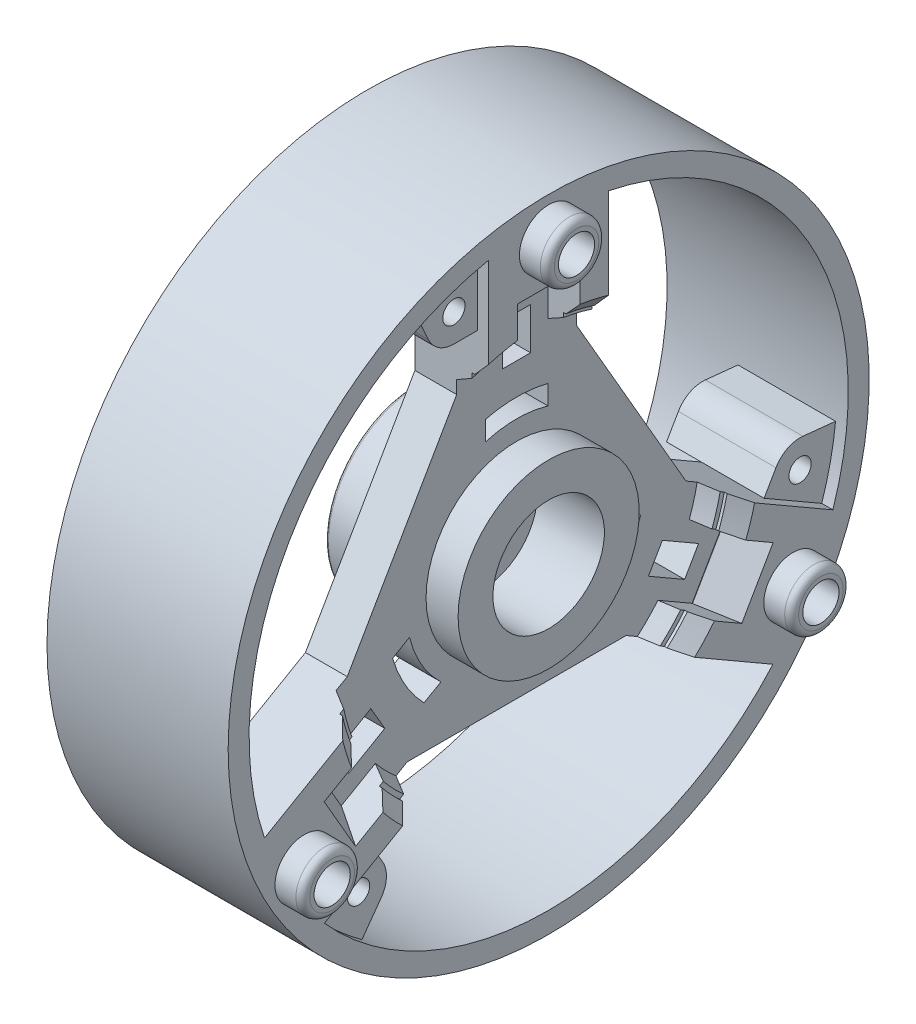
SolidWorks part; units mm, degrees
ref_plane "Front" through (0, 0, 0) normal (0, 0, 1) x (1, 0, 0)
ref_plane "Top" through (0, 0, 0) normal (0, 1, 0) x (1, 0, 0)
ref_plane "Right" through (0, 0, 0) normal (1, 0, 0) x (0, 0, -1)
sketch "草图1" plane through (0, 0, 0) normal (0, 0, 1) x (1, 0, 0)
  line L0 (-28.9493, 0) -> (20.3261, 0) construction
  line L1 (0, 28.587) -> (0, -29.6739) construction
  line L2 (-13, 23) -> (0, 23)
  line L3 (0, 23) -> (0, 21.5)
  line L4 (0, 21.5) -> (-2.3, 21.5)
  line L5 (-2.3, 21.5) -> (-2.3, 6.5)
  line L6 (-2.3, 6.5) -> (0, 6.5)
  line L7 (0, 6.5) -> (0, 4)
  line L8 (0, 4) -> (-4.8, 4)
  line L9 (-4.8, 4) -> (-4.8, 2.5)
  line L10 (-4.8, 2.5) -> (-9.5, 2.5)
  line L11 (-9.5, 2.5) -> (-9.5, 6.5)
  line L12 (-9.5, 6.5) -> (-5.3, 6.5)
  line L13 (-5.3, 6.5) -> (-5.3, 21.5)
  line L14 (-5.3, 21.5) -> (-13, 21.5)
  line L15 (-13, 21.5) -> (-13, 23)
  point P7 (0, 22.25)
  dimension "D1" = 46
  dimension "D2" = 5
  dimension "D3" = 8
  dimension "D4" = 4.8
  dimension "D5" = 9.5
  dimension "D6" = 2.3
  dimension "D7" = 3
  dimension "D8" = 13
  dimension "D9" = 43
  dimension "D10" = 1.5
  dimension "D11" = 13
revolve "旋转1" add sketch "草图1" angle 360 about L0
sketch "草图2" plane through (-2.3, 0, 0) normal (1, 0, 0) x (0, 0, -1)
  line L0 (-28.8225, 0) -> (32.6158, 0) construction
  line L1 (0, 27.0503) -> (0, -29.2143) construction
  line L2 (0, 0) -> (-26.977, 15.5752) construction
  line L3 (0, 0) -> (25.1673, 14.5303) construction
  line L4 (-4.3, 21.0656) -> (-4.3, 11.5522)
  line L5 (4.3, 21.0656) -> (4.3, 11.5522) construction
  line L6 (0, 0) -> (-25.6049, -14.783) construction
  line L7 (-20.3934, -6.8089) -> (-12.1545, -2.0522)
  line L8 (-4.3, 11.5522) -> (-12.1545, -2.0522)
  circle A0 centre (0, 0) radius 21.5 construction
  arc A1 (-4.3, 21.0656) -> (-20.3934, -6.8089) centre (0, 0) ccw
  dimension "D1" = 60
  dimension "D2" = 60
  dimension "D3" = 8.6
  dimension "D4" = 60
  dimension "D5" = 4.3
  dimension "D6" = 4.3
  dimension "D7" = 9.5
extrude "切除-拉伸1" cut sketch "草图2" against normal blind 10
pattern_circular "阵列(圆周)1" count 3 over 360 about axis through (-28.9493, 0, 0) along (-1, 0, 0) of "切除-拉伸1"
sketch "草图3" plane through (-2.3, 0, 0) normal (1, 0, 0) x (0, 0, -1)
  line L0 (0, 25.0293) -> (0, -25.5268) construction
  line L1 (-29.32, 0) -> (32.0561, 0) construction
  line L2 (-2.25, 8.9728) -> (-2.25, 7.5728)
  line L3 (2.25, 8.9728) -> (2.25, 7.5728)
  line L4 (-1, 14.5) -> (-1, 11.5)
  line L5 (-1, 11.5) -> (1, 11.5)
  line L6 (-1, 14.5) -> (1, 14.5)
  line L7 (1, 14.5) -> (1, 11.5)
  arc A0 (2.25, 7.5728) -> (-2.25, 7.5728) centre (0, 0) ccw
  arc A1 (2.25, 8.9728) -> (-2.25, 8.9728) centre (0, 0) ccw
  point P15 (0, 14.5)
  point P16 (0, 11.5)
  dimension "D2" = 7.9
  dimension "D4" = 2
  dimension "D1" = 4.5
  dimension "D3" = 1.4
  dimension "D5" = 3
  dimension "D6" = 11.5
extrude "切除-拉伸2" cut sketch "草图3" against normal blind 10
pattern_circular "阵列(圆周)2" count 3 over 360 about axis through (-28.9493, 0, 0) along (-1, 0, 0) of "切除-拉伸2"
sketch "草图5" plane through (-2.3, 0, 0) normal (1, 0, 0) x (0, 0, -1)
  line L0 (-30.2528, 0) -> (26.0864, 0) construction
  line L1 (4.3, 21.0656) -> (4.3, 11.5522) construction
  line L2 (-4.3, 11.5522) -> (-4.3, 21.0656) construction
  line L3 (0, 26.901) -> (0, -26.5279) construction
  line L4 (4.3, 21.0656) -> (4.3, 12.2683)
  line L5 (-4.3, 12.2683) -> (-4.3, 21.0656)
  line L6 (-2.25, 15.841) -> (-2.25, 12.8038)
  line L10 (2.25, 15.841) -> (2.25, 12.8038)
  line L11 (-2.25, 15.841) -> (2.25, 15.841)
  arc A0 (4.3, 21.0656) -> (-4.3, 21.0656) centre (0, 0) ccw construction
  arc A1 (4.3, 21.0656) -> (-4.3, 21.0656) centre (0, 0) ccw
  arc A3 (4.3, 12.2683) -> (2.25, 12.8038) centre (0, 0) ccw
  arc A4 (-2.25, 12.8038) -> (-4.3, 12.2683) centre (0, 0) ccw
  dimension "D2" = 15.841
  dimension "D3" = 26
  dimension "D1" = 4.5
  dimension "D4" = 2.25
extrude "凸台-拉伸1" add sketch "草图5" along normal up to surface (2.3 mm away) up to face at (0, 0, 23)
sketch "草图6" plane through (0, 0, 0) normal (0, 0, 1) x (1, 0, 0)
  line L0 (-21.4554, 0) -> (8.5797, 0) construction
  line L1 (0, 29.1471) -> (0, -31.5649) construction
  line L2 (1.205, 18.0728) -> (-2.3, 15.825)
  line L4 (-2.3, 15.825) -> (1.205, 15.825)
  line L5 (1.205, 15.825) -> (1.205, 18.0728)
  point P9 (0, 17.3)
  point P11 (-2.3, 15.8)
  dimension "D1" = 31.65
  dimension "D2" = 17.3
extrude "切除-拉伸6" cut sketch "草图6" against normal mid plane 4.5
sketch "草图7" plane through (0, 0, 0) normal (0, 0, 1) x (1, 0, 0)
  line L0 (-19.8427, 0) -> (8.4715, 0) construction
  line L1 (0, 26.6452) -> (0, -27.0981) construction
  line L2 (1.1268, 15.2) -> (0, 15.2)
  line L3 (0, 15.2) -> (-1, 14.1244)
  line L5 (-1.2, 13.8) -> (-2.3, 13.2)
  line L7 (1.1268, 13.2) -> (1.1268, 15.2)
  line L8 (-1.2, 13.8) -> (-1.2, 14.1244)
  line L9 (-1.2, 14.1244) -> (-1, 14.1244)
  line L10 (-2.3, 11.5) -> (-2.3, 14.5) construction
  line L11 (-2.3, 13.2) -> (-2.3, 12.3964)
  line L12 (-2.3, 12.3964) -> (1.1268, 12.3964)
  line L13 (1.1268, 12.3964) -> (1.1268, 13.2)
  point P7 (-1.2, 13.9622)
  dimension "D2" = 27.6
  dimension "D3" = 1.1
  dimension "D4" = 30.4
  dimension "D5" = 1
revolve "切除-旋转2" cut sketch "草图7" angle 360 about L0
pattern_circular "阵列(圆周)3" count 3 over 360 about axis through (-4.8, 0, 0) along (-1, 0, 0) of "凸台-拉伸1", "切除-拉伸6", "切除-旋转2"
sketch "草图8" plane through (0, 0, 0) normal (1, 0, 0) x (0, 0, -1)
  line L0 (-28.3188, 0) -> (29.8859, 0) construction
  line L1 (0, 26.9885) -> (0, -27.3255) construction
  line L2 (0, 0) -> (-21.8667, -12.6247) construction
  line L3 (0, 0) -> (23.8526, -13.7713) construction
  circle A0 centre (0, 0) radius 20.25 construction
  circle A1 centre (0, 20.25) radius 2.1
  circle A2 centre (0, 20.25) radius 1.3
  point P7 (0, 20.25)
  point P10 (17.537, -10.125)
  point P11 (-17.537, -10.125)
  dimension "D1" = 40.5
  dimension "D5" = 4.2
  dimension "D6" = 2.6
  dimension "D2" = 120
  dimension "D3" = 120
  dimension "D4" = 35.074
extrude "凸台-拉伸2" add sketch "草图8" along normal blind 2
fillet "圆角1" radius 0.5 1 edges at (2, 20.25, -2.1)
pattern_circular "阵列(圆周)4" count 3 over 360 about axis through (-4.8, 0, 0) along (-1, 0, 0) of "凸台-拉伸2", "圆角1"
sketch "草图9" plane through (0, 0, 0) normal (1, 0, 0) x (0, 0, -1)
  circle A0 centre (17.537, -10.125) radius 1.3 construction
  circle A1 centre (-17.537, -10.125) radius 1.3 construction
  circle A2 centre (0, 20.25) radius 1.3 construction
  circle A3 centre (17.537, -10.125) radius 1.3
  circle A4 centre (-17.537, -10.125) radius 1.3
  circle A5 centre (0, 20.25) radius 1.3
extrude "切除-拉伸7" cut sketch "草图9" against normal blind 32
sketch "草图10" plane through (-5.3, 0, 0) normal (-1, 0, 0) x (0, 0, 1)
  line L0 (0, 24.7805) -> (0, -25.4024) construction
  line L1 (-28.0995, 0) -> (27.9939, 0) construction
  circle A0 centre (0, 0) radius 20.25 construction
  circle A1 centre (0, 20.25) radius 2
  dimension "D1" = 4
extrude "切除-拉伸8" cut sketch "草图10" against normal blind 2.5 and the other way blind 13
pattern_circular "阵列(圆周)5" count 3 over 360 about axis through (-9.5, 0, 0) along (-1, 0, 0) of "切除-拉伸8"
sketch "草图11" plane through (-2.3, 0, 0) normal (1, 0, 0) x (0, 0, -1)
  line L0 (-26.273, 0) -> (28.6982, 0) construction
  line L1 (0, 31.1171) -> (0, -28.4308) construction
  line L2 (-6, 30.2021) -> (-6, 13.113) construction
  line L3 (-4.3, 16.291) -> (-6, 16.291)
  line L5 (-4.3, 14.5791) -> (-4.3, 21.0656) construction
  line L6 (-4.3, 16.291) -> (-4.3, 21.0656)
  line L7 (-7.2957, 16.291) -> (0, 0) construction
  line L8 (-7.8253, 17.4736) -> (-8.7875, 19.6222)
  circle A1 centre (0, 0) radius 19.25 construction
  circle A2 centre (-6, 18.291) radius 0.8
  arc A3 (-4.3, 21.0656) -> (-20.3934, -6.8089) centre (0, 0) ccw construction
  arc A4 (-4.3, 21.0656) -> (-8.7875, 19.6222) centre (0, 0) ccw
  arc A5 (-7.8253, 17.4736) -> (-6, 16.291) centre (-6, 18.291) ccw
  dimension "D2" = 38.5
  dimension "D3" = 1.6
  dimension "D4" = 2
  dimension "D1" = 6
extrude "凸台-拉伸3" add sketch "草图11" along normal blind 1.5 and the other way blind 5.5
pattern_circular "阵列(圆周)6" count 3 over 360 about axis through (-28.9493, 0, 0) along (-1, 0, 0) of "凸台-拉伸3" reverse direction yes
fillet "圆角2" radius 0.2 1 edges at (-9.5, 0, 6.5)
fillet "圆角3" radius 0.2 1 edges at (-5.3, 0, 6.5)
fillet "圆角4" radius 0.2 3 edges at (-5.3, -9.125, 15.805) (-5.3, -9.125, -15.805) (-5.3, 18.25, 0)
